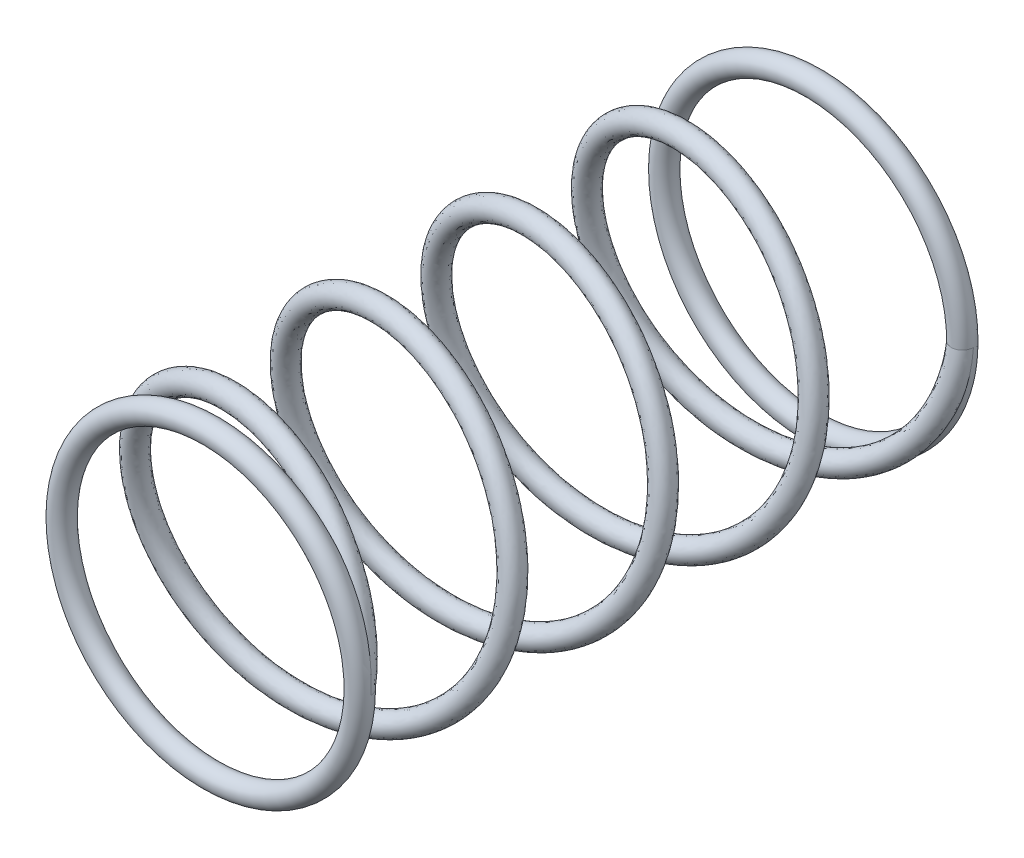
SolidWorks part; units mm, degrees
material "AISI 304"
ref_plane "Front Plane" through (0, 0, 0) normal (0, 0, 1) x (1, 0, 0)
ref_plane "Top Plane" through (0, 0, 0) normal (0, 1, 0) x (1, 0, 0)
ref_plane "Right Plane" through (0, 0, 0) normal (1, 0, 0) x (0, 0, -1)
sketch "Sketch2" plane through (0, 0, 0) normal (0, 0, 1) x (1, 0, 0)
  circle A0 centre (0, 0) radius 4.7
  dimension "D1" = 9.4
curve "Helix/Spiral1" pitch 4.75 height 19 radius 4.7 left hand yes centre (0, 0, 0) axis (0, 0, 1) start towards (1, 0, 0)
sketch "Sketch4" plane through (0, 0, 0) normal (0, 1, 0) x (1, 0, 0)
  circle A0 centre (4.7, 0) radius 0.35
  spline S0 degree 3 poles (4.7, 0) (4.7, -0.0983) (4.4553, -0.2972) (3.4099, -0.5937) (1.8454, -0.8906) (0, -1.1875) (-1.8454, -1.4844) (-3.4099, -1.7812) (-4.4553, -2.0781) (-4.8224, -2.375) (-4.4553, -2.6719) (-3.4099, -2.9687) (-1.3239, -3.3646) (1.3239, -3.7604) (3.4099, -4.1562) (4.4553, -4.4531) (4.8224, -4.75) (4.4553, -5.0469) (3.4099, -5.3437) (1.3239, -5.7396) (-1.3239, -6.1354) (-3.4099, -6.5313) (-4.4553, -6.8281) (-4.8224, -7.125) (-4.4553, -7.4219) (-3.4099, -7.7188) (-1.3239, -8.1146) (1.3239, -8.5104) (3.4099, -8.9063) (4.4553, -9.2031) (4.8224, -9.5) (4.4553, -9.7969) (3.4099, -10.0937) (1.3239, -10.4896) (-1.3239, -10.8854) (-3.4099, -11.2813) (-4.4553, -11.5781) (-4.8224, -11.875) (-4.4553, -12.1719) (-3.4099, -12.4688) (-1.3239, -12.8646) (1.3239, -13.2604) (3.4099, -13.6563) (4.4553, -13.9531) (4.8224, -14.25) (4.4553, -14.5469) (3.4099, -14.8438) (1.3239, -15.2396) (-1.3239, -15.6354) (-3.4099, -16.0313) (-4.4553, -16.3281) (-4.8224, -16.625) (-4.4553, -16.9219) (-3.4099, -17.2188) (-1.8454, -17.5156) (0, -17.8125) (1.8454, -18.1094) (3.4099, -18.4063) (4.4553, -18.7028) (4.7, -18.9017) (4.7, -19) knots 0 0 0 0 0.015625 0.03125 0.046875 0.0625 0.078125 0.09375 0.109375 0.125 0.140625 0.15625 0.171875 0.203125 0.21875 0.234375 0.25 0.265625 0.28125 0.296875 0.328125 0.34375 0.359375 0.375 0.390625 0.40625 0.421875 0.453125 0.46875 0.484375 0.5 0.515625 0.53125 0.546875 0.578125 0.59375 0.609375 0.625 0.640625 0.65625 0.671875 0.703125 0.71875 0.734375 0.75 0.765625 0.78125 0.796875 0.828125 0.84375 0.859375 0.875 0.890625 0.90625 0.921875 0.9375 0.953125 0.96875 0.984375 1 1 1 1 construction
  point P4 (4.7, 0)
  point P5 (4.7, 0)
  point P6 (4.7, 0)
  point P7 (4.7, 0)
  point P8 (4.7, 0)
  dimension "D1" = 0.7
sweep "Sweep1" add profiles "Sketch4" path "Helix/Spiral1"
sweep "Sweep2" add profiles "Sketch4<2>" path "Sketch2<2>"
sketch "Sketch4<2>" plane through (0, 0, 0) normal (0, 1, 0) x (1, 0, 0) same geometry as "Sketch4"
sketch "Sketch2<2>" plane through (0, 0, 0) normal (0, 0, 1) x (1, 0, 0) same geometry as "Sketch2"
ref_plane "Plane1" through (0, 0, 9.5) normal (0, 0, 1) x (1, 0, 0)
mirror "Mirror1" about plane through (0, 0, 9.5) normal (0, 0, 1) of "Sweep2"
